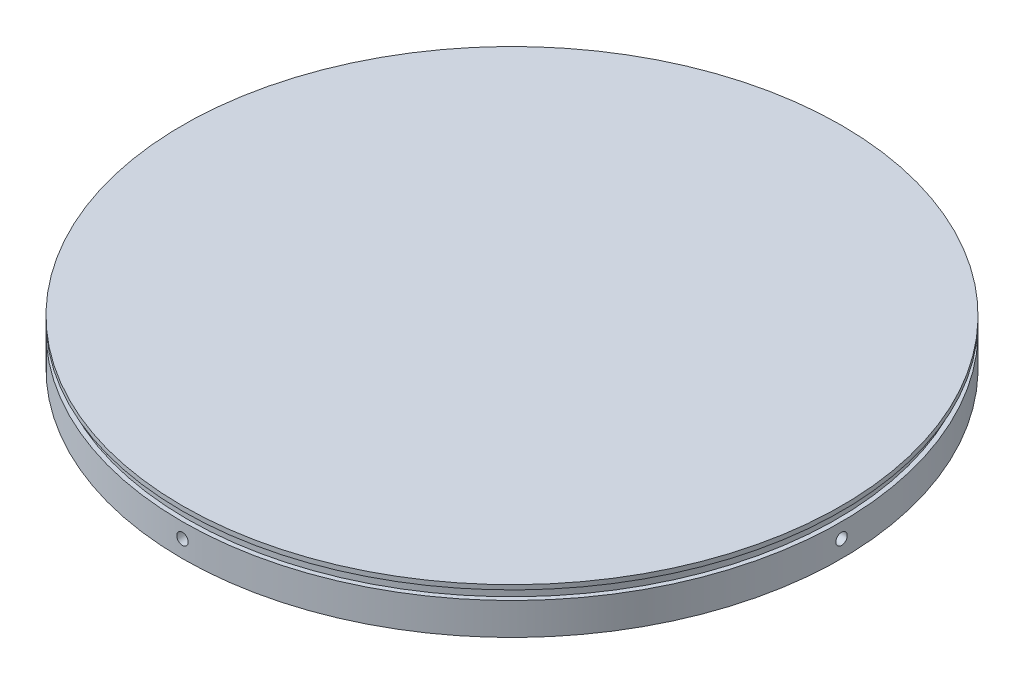
SolidWorks part; units mm, degrees
ref_plane "前基準面" through (0, 0, 0) normal (0, 0, 1) x (1, 0, 0)
ref_plane "上基準面" through (0, 0, 0) normal (0, 1, 0) x (1, 0, 0)
ref_plane "右基準面" through (0, 0, 0) normal (1, 0, 0) x (0, 0, -1)
sketch "草圖9" plane through (0, 0, 0) normal (0, 1, 0) x (1, 0, 0)
  line L0 (0, 0) -> (0, 76.3417) construction
  circle A0 centre (0, 0) radius 66
  circle A1 centre (0, 0) radius 70
  circle A2 centre (0, 0) radius 72
  point P5 (0, 72)
  dimension "D1" = 2
  dimension "D2" = 4
  dimension "D3" = 144
extrude "填料-伸長9" add sketch "草圖9" against normal blind 10 contours A2 A1 region at (-71.7964, 0, 0)
extrude "填料-伸長10" add sketch "草圖9<18>" against normal blind 2.5 contours A1 A0 region at (-68.0201, 0, 0)
sketch "草圖9<18>" plane through (0, 0, 0) normal (0, 1, 0) x (1, 0, 0) same geometry as "草圖9"
extrude "填料-伸長11" add sketch "草圖9<19>" against normal blind 10 contours A0 region at (0, 0, 0)
sketch "草圖9<19>" plane through (0, 0, 0) normal (0, 1, 0) x (1, 0, 0) same geometry as "草圖9"
shell "薄殼2" thickness 2 removed face at (0, -10, 66)
sketch "草圖10" plane through (0, 0, 0) normal (0, 1, 0) x (1, 0, 0)
  circle A0 centre (-54.1329, 0) radius 1.5828
sketch "草圖11" plane through (0, 0, 0) normal (0, 1, 0) x (1, 0, 0)
  line L1 (-34, 34) -> (34, 34)
  line L2 (-34, 34) -> (-34, -34)
  line L3 (-34, -34) -> (34, -34)
  line L4 (34, 34) -> (34, -34)
  line L5 (-34, 34) -> (34, -34) construction
  line L6 (-34, -34) -> (34, 34) construction
  point P0 (0, 0)
  point P7 (-30, 30)
  point P10 (30, 30)
  point P11 (30, -30)
  point P12 (-30, -30)
  point P13 (0, 0)
  dimension "D1" = 68
  dimension "D2" = 4
  dimension "D3" = 4
sketch "草圖13" plane through (0, 0, 0) normal (0, 0, 1) x (1, 0, 0)
  line L0 (0, 0) -> (0, -10) construction
  line L1 (-72, -10) -> (72, -10) construction
  point P5 (0, -6.25)
  dimension "D1" = 3.75
hole_wizard "Ø2.5mm 定位孔1" positions "3D草圖2" profile "草圖14" hole size "Ø2.5" standard "JIS" end condition up to next
sketch3d "3D草圖2"
  point P0 (0, -6.25, 72)
  point P4 (0, 0, 0)
sketch "草圖14" plane through (0, -6.25, 72) normal (1, 0, 0) x (0, -1, 0)
  line L0 (0, 0) -> (0, 8)
  line L1 (0, 8) -> (1.25, 8)
  line L2 (1.25, 8) -> (1.25, 0)
  line L5 (1.25, 0) -> (0, 0)
  line L11 (0, -6.35) -> (0, 107.95) construction
  dimension "貫穿孔直徑" = 2.5
  dimension "貫穿孔深度" = 8
pattern_circular "環狀複製排列1" count 4 over 360 about axis through (0, -10, 0) along (0, 1, 0) of "Ø2.5mm 定位孔1"
ref_plane "平面1" through (0, 0, 0) normal (1, 0, 0) x (0, 0, -1)
sketch "草圖15" plane through (0, 0, 0) normal (1, 0, 0) x (0, 0, -1)
  line L0 (-72, 0) -> (-72, -5.0001) construction
  line L1 (-72, -1) -> (-71, -1)
  line L2 (-72, -1) -> (-72, -3)
  line L3 (-72, -3) -> (-71, -3)
  line L4 (-71, -1) -> (-71, -3)
  line L5 (-72, -1) -> (-71, -3) construction
  line L6 (-72, -3) -> (-71, -1) construction
  line L7 (72, 0) -> (-72, 0) construction
  point P0 (-71.5, -2)
  point P7 (-70.7745, -2.9796)
  dimension "D1" = 1
  dimension "D2" = 2
  dimension "D3" = 1
revolve "除料-旋轉2" cut sketch "草圖15" angle 360 about L0
